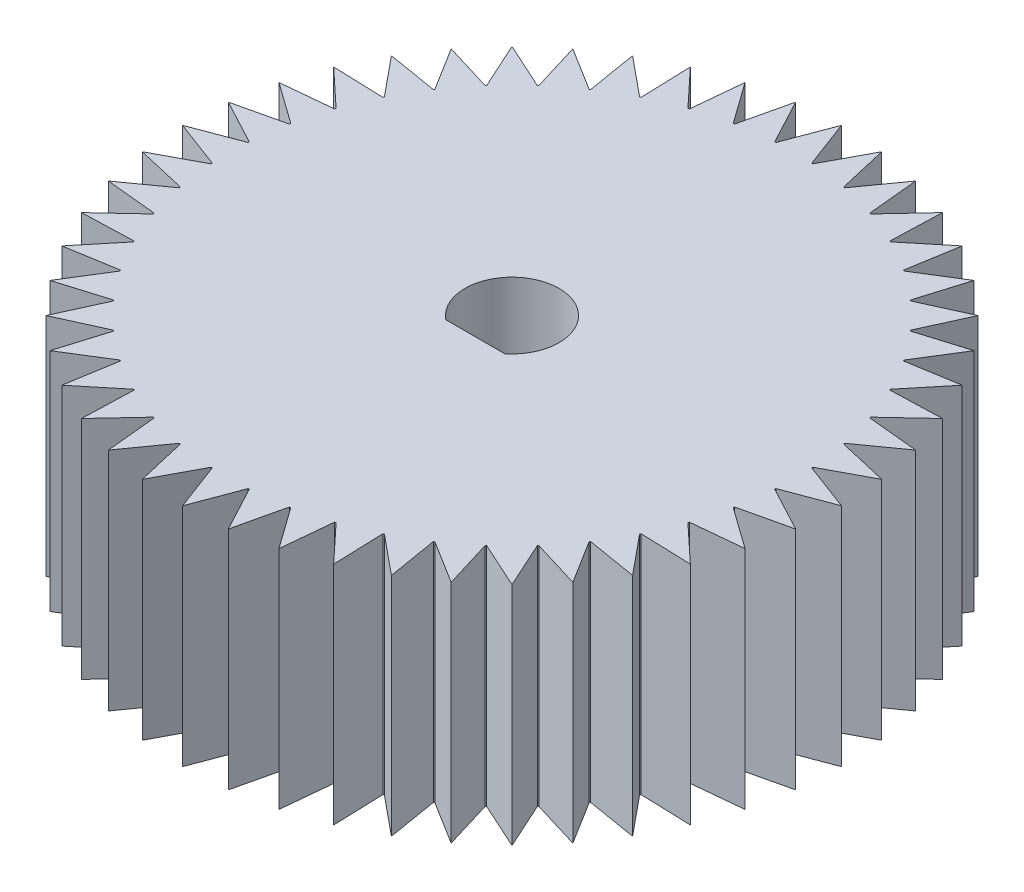
SolidWorks part; units mm, degrees
ref_plane "Спереди" through (0, 0, 0) normal (0, 0, 1) x (1, 0, 0)
ref_plane "Сверху" through (0, 0, 0) normal (0, 1, 0) x (1, 0, 0)
ref_plane "Справа" through (0, 0, 0) normal (1, 0, 0) x (0, 0, -1)
sketch "Эскиз1" plane through (0, 0, 0) normal (0, 1, 0) x (1, 0, 0)
  line L0 (2.2842, 17.3503) -> (2.8954, 14.7179)
  line L1 (1.0126, 14.9658) -> (2.2842, 17.3503)
  line L2 (4.5293, 16.9037) -> (4.7917, 14.2141)
  line L3 (2.9573, 14.7056) -> (4.5293, 16.9037)
  line L222 (-1.5644, -1.95) -> (1.5644, -1.95)
  line L299 (6.697, 16.1679) -> (6.606, 13.467)
  line L303 (4.8515, 14.1938) -> (6.697, 16.1679)
  line L304 (0, 17.5) -> (0.9495, 14.9699)
  line L305 (-0.9495, 14.9699) -> (0, 17.5)
  line L306 (8.75, 15.1554) -> (8.3073, 12.4896)
  line L307 (6.6626, 13.4391) -> (8.75, 15.1554)
  line L308 (10.6533, 13.8837) -> (9.8664, 11.2984)
  line L309 (8.3598, 12.4545) -> (10.6533, 13.8837)
  line L310 (12.3744, 12.3744) -> (11.2567, 9.9139)
  line L311 (9.9139, 11.2567) -> (12.3744, 12.3744)
  line L312 (13.8837, 10.6533) -> (12.4545, 8.3598)
  line L313 (11.2984, 9.8664) -> (13.8837, 10.6533)
  line L314 (15.1554, 8.75) -> (13.4391, 6.6626)
  line L315 (12.4896, 8.3073) -> (15.1554, 8.75)
  line L316 (16.1679, 6.697) -> (14.1938, 4.8515)
  line L317 (13.467, 6.606) -> (16.1679, 6.697)
  line L318 (16.9037, 4.5293) -> (14.7056, 2.9573)
  line L319 (14.2141, 4.7917) -> (16.9037, 4.5293)
  line L320 (17.3503, 2.2842) -> (14.9658, 1.0126)
  line L321 (14.7179, 2.8954) -> (17.3503, 2.2842)
  line L322 (17.5, 0) -> (14.9699, -0.9495)
  line L323 (14.9699, 0.9495) -> (17.5, 0)
  line L324 (17.3503, -2.2842) -> (14.7179, -2.8954)
  line L325 (14.9658, -1.0126) -> (17.3503, -2.2842)
  line L326 (16.9037, -4.5293) -> (14.2141, -4.7917)
  line L327 (14.7056, -2.9573) -> (16.9037, -4.5293)
  line L328 (16.1679, -6.697) -> (13.467, -6.606)
  line L329 (14.1938, -4.8515) -> (16.1679, -6.697)
  line L330 (15.1554, -8.75) -> (12.4896, -8.3073)
  line L331 (13.4391, -6.6626) -> (15.1554, -8.75)
  line L332 (13.8837, -10.6533) -> (11.2984, -9.8664)
  line L333 (12.4545, -8.3598) -> (13.8837, -10.6533)
  line L334 (12.3744, -12.3744) -> (9.9139, -11.2567)
  line L335 (11.2567, -9.9139) -> (12.3744, -12.3744)
  line L336 (10.6533, -13.8837) -> (8.3598, -12.4545)
  line L337 (9.8664, -11.2984) -> (10.6533, -13.8837)
  line L338 (8.75, -15.1554) -> (6.6626, -13.4391)
  line L339 (8.3073, -12.4896) -> (8.75, -15.1554)
  line L340 (6.697, -16.1679) -> (4.8515, -14.1938)
  line L341 (6.606, -13.467) -> (6.697, -16.1679)
  line L342 (4.5293, -16.9037) -> (2.9573, -14.7056)
  line L343 (4.7917, -14.2141) -> (4.5293, -16.9037)
  line L344 (2.2842, -17.3503) -> (1.0126, -14.9658)
  line L345 (2.8954, -14.7179) -> (2.2842, -17.3503)
  line L346 (0, -17.5) -> (-0.9495, -14.9699)
  line L347 (0.9495, -14.9699) -> (0, -17.5)
  line L348 (-2.2842, -17.3503) -> (-2.8954, -14.7179)
  line L349 (-1.0126, -14.9658) -> (-2.2842, -17.3503)
  line L350 (-4.5293, -16.9037) -> (-4.7917, -14.2141)
  line L351 (-2.9573, -14.7056) -> (-4.5293, -16.9037)
  line L352 (-6.697, -16.1679) -> (-6.606, -13.467)
  line L353 (-4.8515, -14.1938) -> (-6.697, -16.1679)
  line L354 (-8.75, -15.1554) -> (-8.3073, -12.4896)
  line L355 (-6.6626, -13.4391) -> (-8.75, -15.1554)
  line L356 (-10.6533, -13.8837) -> (-9.8664, -11.2984)
  line L357 (-8.3598, -12.4545) -> (-10.6533, -13.8837)
  line L358 (-12.3744, -12.3744) -> (-11.2567, -9.9139)
  line L359 (-9.9139, -11.2567) -> (-12.3744, -12.3744)
  line L360 (-13.8837, -10.6533) -> (-12.4545, -8.3598)
  line L361 (-11.2984, -9.8664) -> (-13.8837, -10.6533)
  line L362 (-15.1554, -8.75) -> (-13.4391, -6.6626)
  line L363 (-12.4896, -8.3073) -> (-15.1554, -8.75)
  line L364 (-16.1679, -6.697) -> (-14.1938, -4.8515)
  line L365 (-13.467, -6.606) -> (-16.1679, -6.697)
  line L366 (-16.9037, -4.5293) -> (-14.7056, -2.9573)
  line L367 (-14.2141, -4.7917) -> (-16.9037, -4.5293)
  line L368 (-17.3503, -2.2842) -> (-14.9658, -1.0126)
  line L369 (-14.7179, -2.8954) -> (-17.3503, -2.2842)
  line L370 (-17.5, 0) -> (-14.9699, 0.9495)
  line L371 (-14.9699, -0.9495) -> (-17.5, 0)
  line L372 (-17.3503, 2.2842) -> (-14.7179, 2.8954)
  line L373 (-14.9658, 1.0126) -> (-17.3503, 2.2842)
  line L374 (-16.9037, 4.5293) -> (-14.2141, 4.7917)
  line L375 (-14.7056, 2.9573) -> (-16.9037, 4.5293)
  line L376 (-16.1679, 6.697) -> (-13.467, 6.606)
  line L377 (-14.1938, 4.8515) -> (-16.1679, 6.697)
  line L378 (-15.1554, 8.75) -> (-12.4896, 8.3073)
  line L379 (-13.4391, 6.6626) -> (-15.1554, 8.75)
  line L380 (-13.8837, 10.6533) -> (-11.2984, 9.8664)
  line L381 (-12.4545, 8.3598) -> (-13.8837, 10.6533)
  line L382 (-12.3744, 12.3744) -> (-9.9139, 11.2567)
  line L383 (-11.2567, 9.9139) -> (-12.3744, 12.3744)
  line L384 (-10.6533, 13.8837) -> (-8.3598, 12.4545)
  line L385 (-9.8664, 11.2984) -> (-10.6533, 13.8837)
  line L386 (-8.75, 15.1554) -> (-6.6626, 13.4391)
  line L387 (-8.3073, 12.4896) -> (-8.75, 15.1554)
  line L388 (-6.697, 16.1679) -> (-4.8515, 14.1938)
  line L389 (-6.606, 13.467) -> (-6.697, 16.1679)
  line L390 (-4.5293, 16.9037) -> (-2.9573, 14.7056)
  line L391 (-4.7917, 14.2141) -> (-4.5293, 16.9037)
  line L392 (-2.2842, 17.3503) -> (-1.0126, 14.9658)
  line L393 (-2.8954, 14.7179) -> (-2.2842, 17.3503)
  circle A3 centre (0, 0) radius 15
  arc A6 (-1.5644, -1.95) -> (1.5644, -1.95) centre (0, 0) cw
  point P158 (0, 0)
  point P224 (0, 0)
extrude "Бобышка-Вытянуть5" add sketch "Эскиз1" along normal blind 12 contours A3 | A3 L344 L345 | A3 L342 L343 | A3 L340 L341 | A3 L338 L339 | A3 L336 L337 | A3 L334 L335 | A3 L346 L347 | A3 L348 L349 | A3 L350 L351 | A3 L352 L353 | A3 L354 L355 | A3 L356 L357 | A3 L358 L359 | A3 L360 L361 | A3 L362 L363 | A3 L364 L365 | A3 L366 L367 | A3 L368 L369 | A3 L370 L371 | A3 L372 L373 | A3 L374 L375 | A3 L376 L377 | A3 L378 L379 | A3 L380 L381 | A3 L382 L383 | A3 L384 L385 | A3 L386 L387 | A3 L388 L389 | A3 L390 L391 | A3 L392 L393 | A3 L304 L305 | A3 L0 L1 | A3 L2 L3 | A3 L299 L303 | A3 L306 L307 | A3 L308 L309 | A3 L310 L311 | A3 L312 L313 | A3 L314 L315 | A3 L316 L317 | A3 L318 L319 | A3 L320 L321 | A3 L322 L323 | A3 L324 L325 | A3 L326 L327 | A3 L328 L329 | A3 L330 L331 | A3 L332 L333 region at (2.0658, 0, -15.6913) region at (2.8436, 0, -14.2957) region at (4.0962, 0, -15.2874) region at (0, 0, -15.8267) region at (6.0566, 0, -14.6219) region at (-2.0658, 0, -15.6913) region at (7.9133, 0, -13.7063) region at (-4.0962, 0, -15.2874) region at (9.6347, 0, -12.5561) region at (-6.0566, 0, -14.6219) region at (11.1911, 0, -11.1911) region at (-7.9133, 0, -13.7063) region at (12.5561, 0, -9.6347) region at (-9.6347, 0, -12.5561) region at (13.7063, 0, -7.9133) region at (-11.1911, 0, -11.1911) region at (14.6219, 0, -6.0566) region at (-12.5561, 0, -9.6347) region at (15.2874, 0, -4.0962) region at (-13.7063, 0, -7.9133) region at (15.6913, 0, -2.0658) region at (-14.6219, 0, -6.0566) region at (15.8267, 0, 0) region at (-15.2874, 0, -4.0962) region at (-15.6913, 0, -2.0658) region at (15.6913, 0, 2.0658) region at (-15.8267, 0, 0) region at (15.2874, 0, 4.0962) region at (-15.6913, 0, 2.0658) region at (14.6219, 0, 6.0566) region at (-15.2874, 0, 4.0962) region at (13.7063, 0, 7.9133) region at (-14.6219, 0, 6.0566) region at (12.5561, 0, 9.6347) region at (-13.7063, 0, 7.9133) region at (11.1911, 0, 11.1911) region at (-12.5561, 0, 9.6347) region at (9.6347, 0, 12.5561) region at (-11.1911, 0, 11.1911) region at (7.9133, 0, 13.7063) region at (-9.6347, 0, 12.5561) region at (6.0566, 0, 14.6219) region at (-7.9133, 0, 13.7063) region at (4.0962, 0, 15.2874) region at (-6.0566, 0, 14.6219) region at (2.0658, 0, 15.6913) region at (-4.0962, 0, 15.2874) region at (0, 0, 15.8267) region at (-2.0658, 0, 15.6913)
sketch "Эскиз2" plane through (0, 0, 0) normal (0, 1, 0) x (1, 0, 0)
  circle A0 centre (0, 0) radius 4
extrude "Бобышка-Вытянуть6" add sketch "Эскиз2" against normal blind 4
extrude "Вырез-Вытянуть1" cut sketch "Эскиз1<5>" against normal blind 4 contours A6 L222 region at (0, 0, -0.1383)
sketch "Эскиз1<5>" plane through (0, 0, 0) normal (0, 1, 0) x (1, 0, 0) same geometry as "Эскиз1"
